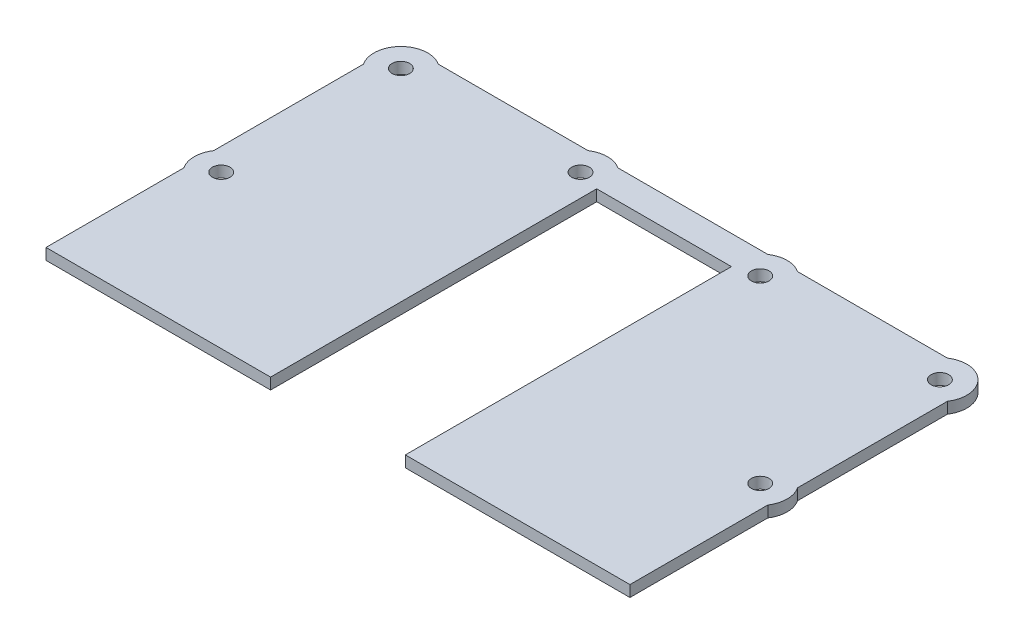
SolidWorks part; units mm, degrees
material "UHMW"
ref_plane "Front Plane" through (0, 0, 0) normal (0, 0, 1) x (1, 0, 0)
ref_plane "Top Plane" through (0, 0, 0) normal (0, 1, 0) x (1, 0, 0)
ref_plane "Right Plane" through (0, 0, 0) normal (1, 0, 0) x (0, 0, -1)
other "Bounding Box"
ref_plane "Default Plane" through (0, 2.286, 19.05) normal (0, -1, 0) x (-1, 0, 0)
sketch "Sketch1" plane through (0, 0, 0) normal (0, 1, 0) x (1, 0, 0)
  line L0 (-103.7379, 114.3) -> (-61.3621, 114.3)
  line L1 (-165.1, 0) -> (-101.6, 0)
  line L2 (0, 0) -> (-63.5, 0)
  line L3 (-101.6, 0) -> (-101.6, 106.172)
  line L4 (-101.6, 106.172) -> (-63.5, 106.172)
  line L5 (-63.5, 106.172) -> (-63.5, 0)
  circle A0 centre (-6.35, 57.15) radius 2.4892
  circle A1 centre (-6.35, 107.95) radius 2.4892
  circle A2 centre (-57.15, 107.95) radius 2.4892
  circle A3 centre (-107.95, 107.95) radius 2.4892
  circle A4 centre (-158.75, 107.95) radius 2.4892
  circle A5 centre (-158.75, 57.15) radius 2.4892
  line B0 (0, 52.9379) -> (0, 0)
  line B1 (0, 103.7379) -> (0, 61.3621)
  line B2 (-52.9379, 114.3) -> (-10.5621, 114.3)
  line B3 (-154.5379, 114.3) -> (-112.1621, 114.3)
  line B4 (-165.1, 61.3621) -> (-165.1, 103.7379)
  line B5 (-165.1, 0) -> (-165.1, 52.9379)
  circle B6 centre (-158.75, 57.15) radius 2.0193
  circle B7 centre (-158.75, 107.95) radius 2.0193
  circle B8 centre (-107.95, 107.95) radius 2.0193
  circle B9 centre (-57.15, 107.95) radius 2.0193
  circle B10 centre (-6.35, 107.95) radius 2.0193
  circle B11 centre (-6.35, 57.15) radius 2.0193
  arc B12 (0, 52.9379) -> (0, 61.3621) centre (-6.35, 57.15) ccw
  arc B13 (0, 103.7379) -> (-10.5621, 114.3) centre (-6.35, 107.95) ccw
  arc B14 (-52.9379, 114.3) -> (-61.3621, 114.3) centre (-57.15, 107.95) ccw
  arc B15 (-103.7379, 114.3) -> (-112.1621, 114.3) centre (-107.95, 107.95) ccw
  arc B16 (-154.5379, 114.3) -> (-165.1, 103.7379) centre (-158.75, 107.95) ccw
  arc B17 (-165.1, 61.3621) -> (-165.1, 52.9379) centre (-158.75, 57.15) ccw
  dimension "D1" = 4.9784
  dimension "D2" = 4.9784
  dimension "D3" = 4.9784
  dimension "D4" = 4.9784
  dimension "D5" = 4.9784
  dimension "D6" = 4.9784
  dimension "D7" = 63.5
  dimension "D8" = 8.128
sketch_block_instance "Block-bottomplateblock-1"
sketch_block "Block-bottomplateblock"
extrude "Boss-Extrude1" add sketch "Sketch1" along normal blind 3.175 contours B4 B17 B5 L1 L3 L4 L5 L2 B0 B12 B1 B13 B2 B14 L0 B15 B3 B16 A0 A1 A2 A3 A4 A5 region at (-82.55, 0, -112.2638)
sketch "Sketch2" plane through (0, 3.175, 0) normal (0, 1, 0) x (1, 0, 0)
  line L0 (0, 52.9379) -> (0, 0) construction
  line L1 (-165.1, 0) -> (0, 0)
  line L2 (-165.1, 0) -> (-165.1, 13.97)
  line L3 (-165.1, 13.97) -> (0, 13.97)
  line L4 (0, 0) -> (0, 13.97)
  dimension "D1" = 13.97
extrude "Cut-Extrude1" cut sketch "Sketch2" against normal through all
equation "\"Unit Measure\"= \"BoundingVolume\" / \"Thickness\"'in^2"
